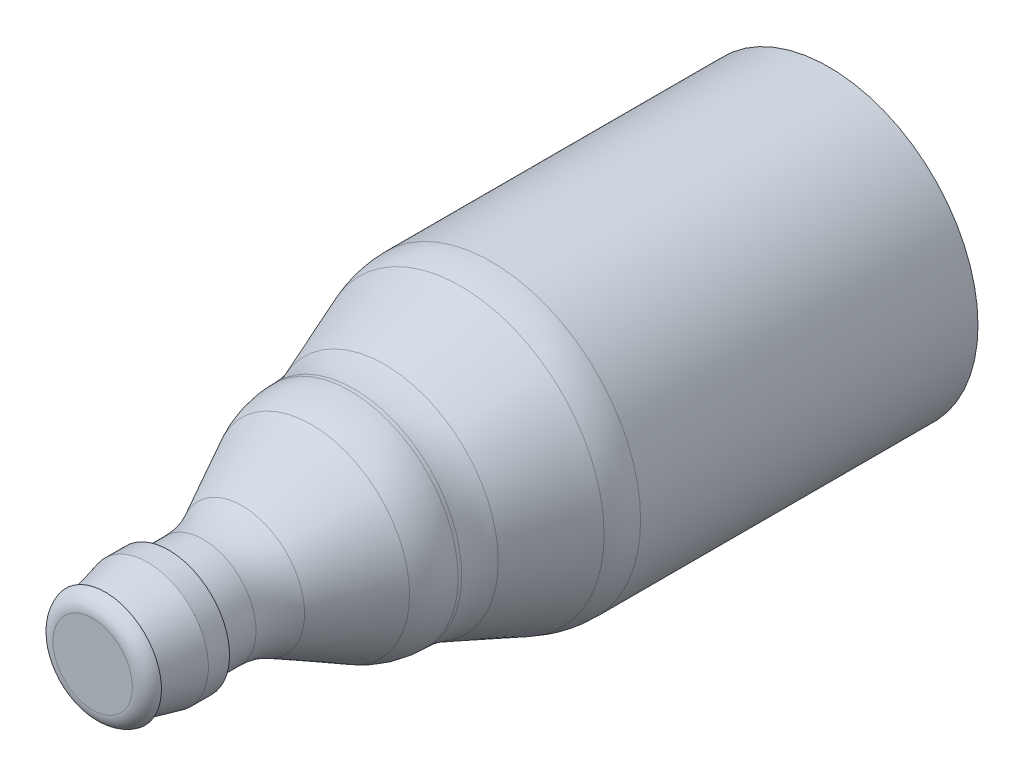
SolidWorks part; units mm, degrees
ref_plane "Plan de face" through (0, 0, 0) normal (0, 0, 1) x (1, 0, 0)
ref_plane "Plan de dessus" through (0, 0, 0) normal (0, 1, 0) x (1, 0, 0)
ref_plane "Plan de droite" through (0, 0, 0) normal (1, 0, 0) x (0, 0, -1)
sketch "Esquisse1" plane through (0, 0, 0) normal (0, 0, 1) x (1, 0, 0)
  circle A0 centre (0, 0) radius 35.25
  dimension "D1" = 70.5
extrude "Boss.-Extru.1" add sketch "Esquisse1" along normal blind 10
sketch "Esquisse2" plane through (0, 0, 0) normal (0, 1, 0) x (1, 0, 0)
  line L0 (0, 0) -> (0, -80.0387) construction
  line L1 (0, 0) -> (-35.25, 0)
  line L2 (-35.25, 0) -> (-35.25, -83.5)
  line L3 (-35.25, -83.5) -> (-25.5, -108.5)
  line L4 (-25.5, -108.5) -> (-25.5, -118)
  line L5 (-25.5, -118) -> (-12.5, -143)
  line L6 (-12.5, -143) -> (-12.5, -156)
  line L7 (-12.5, -156) -> (-14.35, -156)
  line L8 (-14.35, -156) -> (-14.35, -161)
  line L9 (-14.35, -161) -> (-12, -171)
  line L10 (-12, -171) -> (-13.25, -171)
  line L11 (-13.25, -171) -> (-12.5, -174)
  line L12 (-12.5, -174) -> (0, -174)
  line L13 (0, 0) -> (0, -174)
  point P3 (-32.1124, -171.0007)
  point P5 (-13.5, -169.1712)
  point P17 (-16.9043, -156)
  point P18 (-14.331, -163.7256)
  point P19 (-7.1198, -174)
  point P20 (-17.657, -168.5523)
  point P21 (-25.3232, -124.5684)
  point P22 (0, 0)
  point P23 (-12.8683, -169.0026)
  point P24 (-12.5, -170.5073)
  point P25 (-27.8274, -113)
  point P26 (0, 0)
  point P27 (0, -174)
  point P28 (-14.35, -158.7184)
  point P29 (-10.6768, -169.0238)
  point P30 (-12, -171)
  point P31 (-13.25, -171)
  point P32 (-12.5, -174)
  point P33 (-13.25, -171)
  point P34 (-15.3215, -113)
  point P35 (-35.25, -83.5)
  point P36 (-25.5, -86.1623)
  point P37 (-25.5, -90.8725)
  point P38 (-12.5, -139.574)
  point P39 (-25.5, -98.8976)
  point P40 (-16.8956, -124.2954)
  point P41 (-27.892, -104.1565)
  point P42 (-16.9044, -124.258)
  point P43 (-23.9478, -125.4114)
  point P44 (-17.2671, -122.7145)
  point P45 (-20.8671, -94.3448)
  point P46 (-19.649, -127.3545)
  dimension "D1" = 83.5
  dimension "D2" = 70.5
  dimension "D3" = 31
  dimension "D4" = 156
  dimension "D5" = 174
  dimension "D6" = 25
  dimension "D7" = 25
  dimension "D8" = 25
  dimension "D9" = 14.35
  dimension "D10" = 13.25
  dimension "D11" = 12
  dimension "D12" = 15
  dimension "D13" = 5
  dimension "D14" = 25.5
  dimension "D15" = 56
revolve "Révolution1" add sketch "Esquisse2" angle 360 about L0
fillet "Congé1" radius 4 1 edges at (-12.5, 0, 174)
fillet "Congé2" radius 20 4 edges at (-25.5, 0, 108.5) (-35.25, 0, 83.5) (-25.5, 0, 118) (-12.5, 0, 143)
sketch "Esquisse3" plane through (0, 0, 0) normal (0, 0, -1) x (-1, 0, 0)
  point P0 (0, 0)
